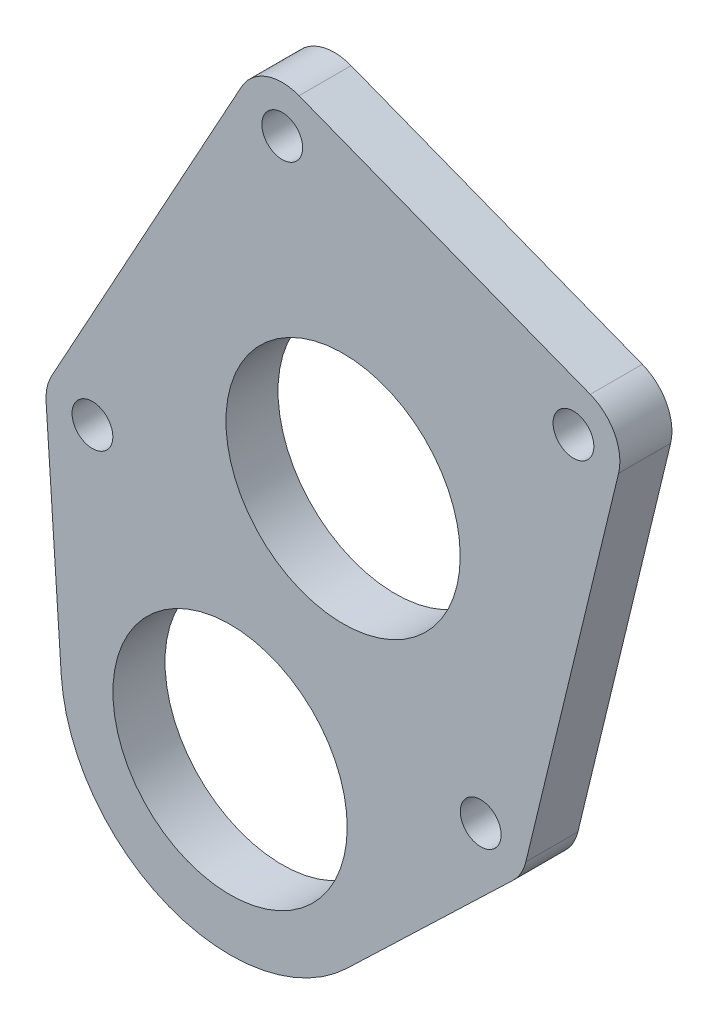
SolidWorks part; units mm, degrees
material "6061-T6 (SS)"
ref_plane "Front Plane" through (0, 0, 0) normal (0, 0, 1) x (1, 0, 0)
ref_plane "Top Plane" through (0, 0, 0) normal (0, 1, 0) x (1, 0, 0)
ref_plane "Right Plane" through (0, 0, 0) normal (1, 0, 0) x (0, 0, -1)
sketch "Sketch1" plane through (0, 0, 0) normal (0, 0, 1) x (1, 0, 0)
  line L0 (13.7841, 35.5191) -> (0, 0) construction
  line L1 (-16.7874, 26.949) -> (30.5715, 8.5702) construction
  line L2 (13.7841, 35.5191) -> (24.1222, 62.1585) construction
  line L3 (0, 0) -> (23.1556, 0) construction
  line L4 (-22.4392, 26.5754) -> (-20.5926, -1.3612)
  line L5 (14.2836, -14.8958) -> (34.4918, 4.4818)
  line L8 (6.3626, 69.0505) -> (41.8817, 55.2664) construction
  line L9 (-21.7507, 29.6781) -> (1.3992, 71.7797)
  line L10 (36.0765, 7.2368) -> (47.3868, 53.9331)
  line L11 (8.4118, 74.331) -> (43.931, 60.5469)
  circle A0 centre (0, 0) radius 14.2875
  circle A1 centre (13.7841, 35.5191) radius 14.2875
  circle A2 centre (-16.7874, 26.949) radius 2.4892
  circle A3 centre (30.5715, 8.5702) radius 2.4892
  arc A5 (-20.5926, -1.3612) -> (14.2836, -14.8958) centre (0, 0) ccw
  circle A9 centre (0, 0) radius 20.6375 construction
  circle A10 centre (41.8817, 55.2664) radius 2.4892
  circle A11 centre (6.3626, 69.0505) radius 2.4892
  arc A12 (-21.7507, 29.6781) -> (-22.4392, 26.5754) centre (-16.7874, 26.949) ccw
  arc A13 (34.4918, 4.4818) -> (36.0765, 7.2368) centre (30.5715, 8.5702) ccw
  arc A14 (47.3868, 53.9331) -> (43.931, 60.5469) centre (41.8817, 55.2664) ccw
  arc A15 (8.4118, 74.331) -> (1.3992, 71.7797) centre (6.3626, 69.0505) ccw
  circle A16 centre (-16.7874, 26.949) radius 5.6642 construction
  circle A17 centre (30.5715, 8.5702) radius 5.6642 construction
  circle A18 centre (41.8817, 55.2664) radius 5.6642 construction
  circle A19 centre (6.3626, 69.0505) radius 5.6642 construction
  point P11 (6.892, 17.7596)
  point P12 (6.892, 17.7596)
  point P17 (24.1222, 62.1585)
  dimension "D1" = 28.575
  dimension "D3" = 4.9784
  dimension "D2" = 38.1
  dimension "D4" = 28.575
  dimension "D5" = 50.8
  dimension "D6" = 68.79
  dimension "D8" = 38.1
  dimension "D7" = 6.35
  dimension "D9" = 3.175
extrude "Boss-Extrude1" add sketch "Sketch1" along normal mid plane 6.35
equation "\"D2@Sketch1\"=60/40"
